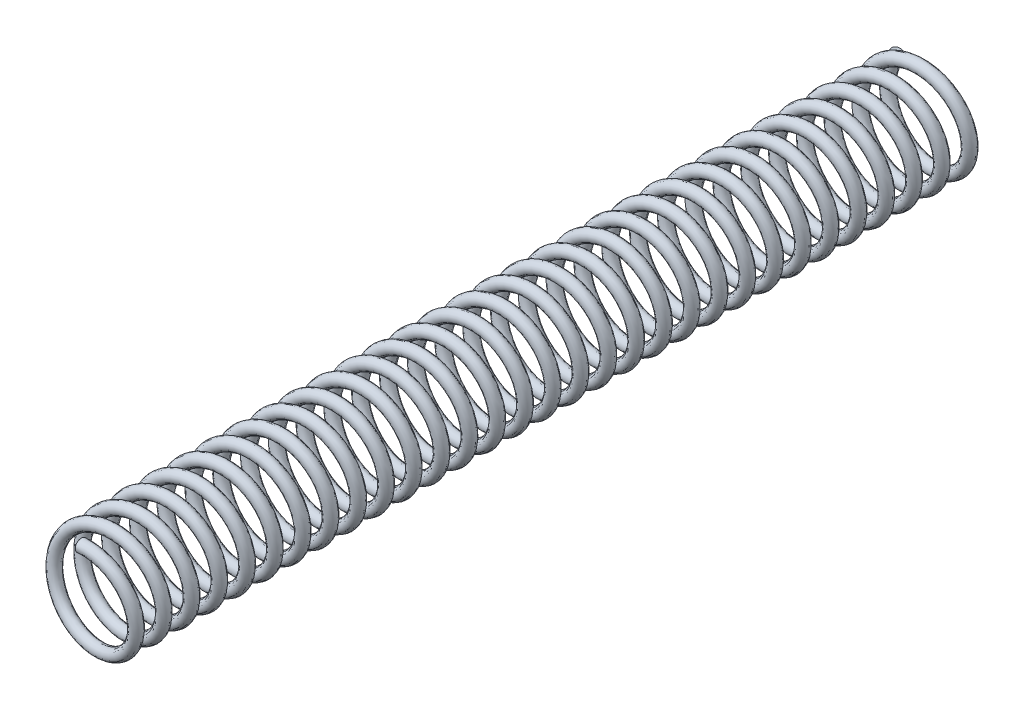
SolidWorks part; units mm, degrees
ref_plane "Front" through (0, 0, 0) normal (0, 0, 1) x (1, 0, 0)
ref_plane "Top" through (0, 0, 0) normal (0, 1, 0) x (1, 0, 0)
ref_plane "Right" through (0, 0, 0) normal (1, 0, 0) x (0, 0, -1)
sketch "Sketch1" plane through (0, 0, 0) normal (0, 1, 0) x (1, 0, 0)
  line L0 (3.5306, 75.311) -> (3.5306, 74.8665) construction
  line L1 (0, 0) -> (3.5306, 0) construction
  line L2 (0, 0) -> (0, 75.311) construction
  line L3 (0, 75.311) -> (3.5306, 75.311) construction
  line L4 (3.5306, 74.8665) -> (3.5306, 74.8411) construction
  line L5 (3.5306, 74.8411) -> (3.5306, 73.9521) construction
  line L6 (3.5306, 73.9521) -> (3.5306, 1.3589) construction
  line L7 (3.5306, 1.3589) -> (3.5306, 0.4699) construction
  line L8 (3.5306, 0.4699) -> (3.5306, 0.4445) construction
  line L9 (3.5306, 0.4445) -> (3.5306, 0) construction
  line L10 (3.5306, 0) -> (3.9751, 0) construction
  line L11 (3.5306, 0.9144) -> (3.9751, 0.9144) construction
  line L12 (3.5306, 75.311) -> (3.9751, 75.311) construction
  line L13 (3.5306, 75.311) -> (3.5306, 75.7555) construction
  line L14 (3.5306, 0) -> (3.5306, -0.4445) construction
  circle A0 centre (3.5306, 75.311) radius 0.4445 construction
  circle A1 centre (3.5306, 74.3966) radius 0.4445 construction
  circle A2 centre (3.5306, 0.9144) radius 0.4445
  circle A3 centre (3.5306, 0) radius 0.4445 construction
  dimension "D3" = 73.4822
  dimension "D1" = 0.0254
  dimension "Spring-OD" = 7.9502
  dimension "D4" = 0.9144
  dimension "Overall Height" = 76.2
ref_plane "Plane1" through (0, 0, -0.9144) normal (0, 0, 1) x (-1, 0, 0)
ref_plane "Plane2" through (0, 0, -74.3966) normal (0, 0, 1) x (-1, 0, 0)
sketch "Sketch2" [suppressed] plane through (0, 0, -0.9144) normal (0, 0, 1) x (-1, 0, 0)
  circle A0 centre (0, 0) radius 3.9751
curve "Helix1" [suppressed] pitch 2.0412 height 73.4822 turns 36
sketch "Sketch3" [suppressed] plane through (0, 0, -0.9144) normal (0, 0, 1) x (-1, 0, 0)
  circle A0 centre (0, 0) radius 3.9751 construction
  circle A1 centre (0, 0) radius 3.9751
curve "Helix2" [suppressed] pitch 0.9144 height 0.9144 turns 1
sketch "Sketch4" [suppressed] plane through (0, 0, -74.3966) normal (0, 0, 1) x (-1, 0, 0)
  circle A0 centre (0, 0) radius 3.9751 construction
  circle A1 centre (0, 0) radius 3.9751
curve "Helix3" [suppressed] pitch 0.9144 height 0.9144 turns 1
sketch "Sketch5" [suppressed] plane through (0, 0, 0) normal (0, 1, 0) x (1, 0, 0)
  line L0 (3.5306, -0.4445) -> (3.5306, 75.7555) construction
  line L1 (3.0861, 0) -> (3.9751, 0) construction
  circle A0 centre (3.5306, 0) radius 0.4445 construction
  circle A1 centre (3.5306, 0) radius 0.4445
curve "CompCurve1" [suppressed]
sweep "Sweep1" [suppressed] add profiles "Sketch5" path "CompCurve1"
sketch "Sketch6" plane through (0, 0, 0) normal (0, 0, 1) x (1, 0, 0)
  circle A0 centre (0, 0) radius 3.9751
curve "Helix/Spiral2" pitch 2.0595 height 63.5 radius 3.9751 centre (0, 0, 0) axis (0, 0, -1) start towards (0, 1, 0)
sketch "Sketch7" plane through (0, 0, 0) normal (0, 1, 0) x (1, 0, 0)
  line L0 (3.5306, -0.4445) -> (3.5306, 75.7555) construction
  line L1 (3.0861, 0) -> (3.9751, 0) construction
  circle A1 centre (3.5306, 0) radius 0.4445
sweep "Sweep2" add profiles "Sketch7" path "Helix/Spiral2"
equation "\"D3@Helix1\"=\"D3@Sketch1\""
equation "\"D3@Helix2\"=\"D4@Sketch1\""
equation "\"D3@Helix3\"=\"D4@Sketch1\""
